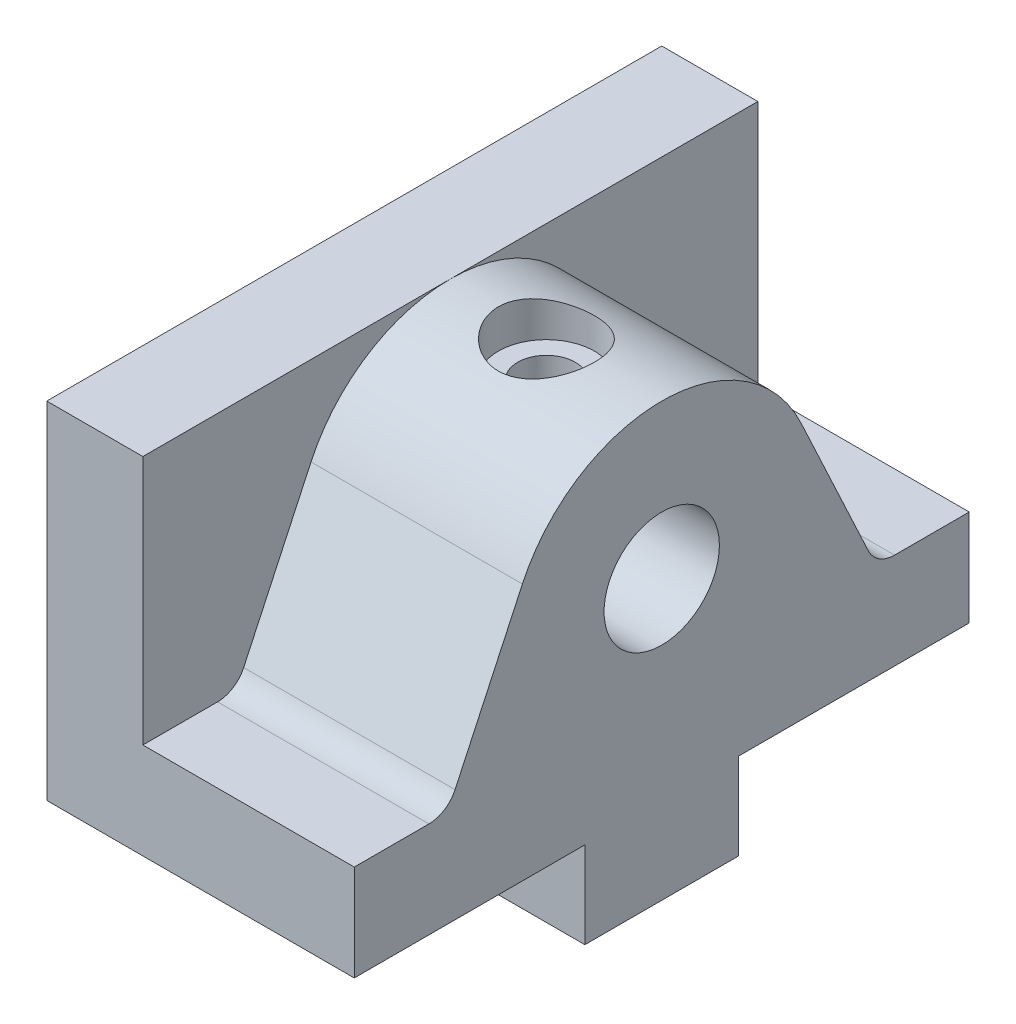
SolidWorks part; units mm, degrees
ref_plane "Front Plane" through (0, 0, 0) normal (0, 0, 1) x (1, 0, 0)
ref_plane "Top Plane" through (0, 0, 0) normal (0, 1, 0) x (1, 0, 0)
ref_plane "Right Plane" through (0, 0, 0) normal (1, 0, 0) x (0, 0, -1)
sketch "Sketch1" plane through (0, 0, 0) normal (0, 0, 1) x (1, 0, 0)
  line L0 (0, 36) -> (0, 0)
  line L1 (0, 0) -> (32, 0)
  line L2 (32, 0) -> (32, 10)
  line L3 (32, 10) -> (10, 10)
  line L4 (10, 10) -> (10, 36)
  line L5 (10, 36) -> (0, 36)
  dimension "D1" = 36
  dimension "D2" = 10
  dimension "D3" = 10
  dimension "D4" = 32
extrude "Boss-Extrude1" add sketch "Sketch1" along normal mid plane 64
sketch "Sketch3" plane through (32, 0, 0) normal (1, 0, 0) x (0, 0, -1)
  line L0 (-32, 36) -> (32, 36) construction
  line L1 (14.5009, 26.7619) -> (21.5094, 11.7321)
  line L2 (-32, 10) -> (32, 10) construction
  line L3 (-14.5009, 26.7619) -> (-21.5094, 11.7321)
  line L4 (-32, 10) -> (32, 10) construction
  line L5 (0, 42.5782) -> (0, -12.609) construction
  line L8 (-24.2283, 10) -> (24.2283, 10)
  arc A0 (14.5009, 26.7619) -> (-14.5009, 26.7619) centre (0, 20) ccw
  circle A1 centre (0, 20) radius 6
  arc A2 (-24.2283, 10) -> (-21.5094, 11.7321) centre (-24.2283, 13) ccw
  arc A3 (21.5094, 11.7321) -> (24.2283, 10) centre (24.2283, 13) ccw
  point P19 (-22.3171, 10)
  point P24 (22.3171, 10)
  dimension "D1" = 32
  dimension "D2" = 12
  dimension "D5" = 3
  dimension "D6" = 3
  dimension "D3" = 50
  dimension "D4" = 25
extrude "Boss-Extrude2" add sketch "Sketch3" against normal up to next contours L3 A2 L8 A3 L1 A0
extrude "Cut-Extrude1" cut sketch "Sketch3<4>" against normal blind 24 contours A1
sketch "Sketch3<4>" plane through (32, 0, 0) normal (1, 0, 0) x (0, 0, -1) same geometry as "Sketch3"
sketch "Sketch4" plane through (32, 0, 0) normal (1, 0, 0) x (0, 0, -1)
  line L0 (-8, -9) -> (8, -9)
  line L1 (-32, 0) -> (32, 0) construction
  line L2 (-8, -9) -> (-8, 0)
  line L3 (-8, 0) -> (8, 0)
  line L4 (8, 0) -> (8, -9)
  point P3 (0, -9)
  dimension "D1" = 16
  dimension "D2" = 9
extrude "Boss-Extrude3" add sketch "Sketch4" against normal blind 32
hole_wizard "Ø6.0mm Dowel Hole1" positions "Sketch5" profile "Sketch6" hole size "Ø6.0" standard "ISO"
sketch "Sketch5" plane through (0, -9, 0) normal (0, -1, 0) x (-1, 0, 0)
  line L0 (-32, -8) -> (-32, 8) construction
  point P0 (-8, 0)
  point P2 (-24, 0)
  dimension "D1" = 8
  dimension "D2" = 16
sketch "Sketch6" plane through (8, -9, 0) normal (1, 0, 0) x (0, 0, -1)
  line L0 (0, 0) -> (0, 17.8026)
  line L1 (0, 17.8026) -> (3, 16)
  line L2 (3, 16) -> (3, 0)
  line L5 (3, 0) -> (0, 0)
  line L10 (0, 17.8026) -> (-3, 16) construction
  line L11 (0, -6.35) -> (0, 107.95) construction
  dimension "Hole Dia." = 6
  dimension "Hole Depth" = 16
  dimension "Drill Angle" = 118
hole_wizard "CBORE for M5 Hex Head Bolt1" positions "3DSketch1" profile "Sketch7" counterbore size "M5" standard "ISO" end condition up to next
sketch3d "3DSketch1"
  line L1 (10, 36, 32) -> (0, 36, 32) construction
  line L2 (0, 36, 32) -> (0, 36, -32) construction
  point P0 (20, 36, 0)
  dimension "D1" = 32
  dimension "D2" = 20
sketch "Sketch7" plane through (20, 36, 0) normal (1, 0, 0) x (0, 0, 1)
  line L0 (0, 0) -> (0, 10)
  line L1 (0, 10) -> (3, 10)
  line L3 (3, 10) -> (3, 4)
  line L4 (3, 4) -> (5, 4)
  line L5 (5, 4) -> (5, 0)
  line L7 (5, 0) -> (0, 0)
  line L11 (0, -6.35) -> (0, 107.95) construction
  dimension "Thru Hole Dia." = 6
  dimension "Thru Hole Depth" = 10
  dimension "C'Bore Dia." = 10
  dimension "C'Bore Depth" = 4
